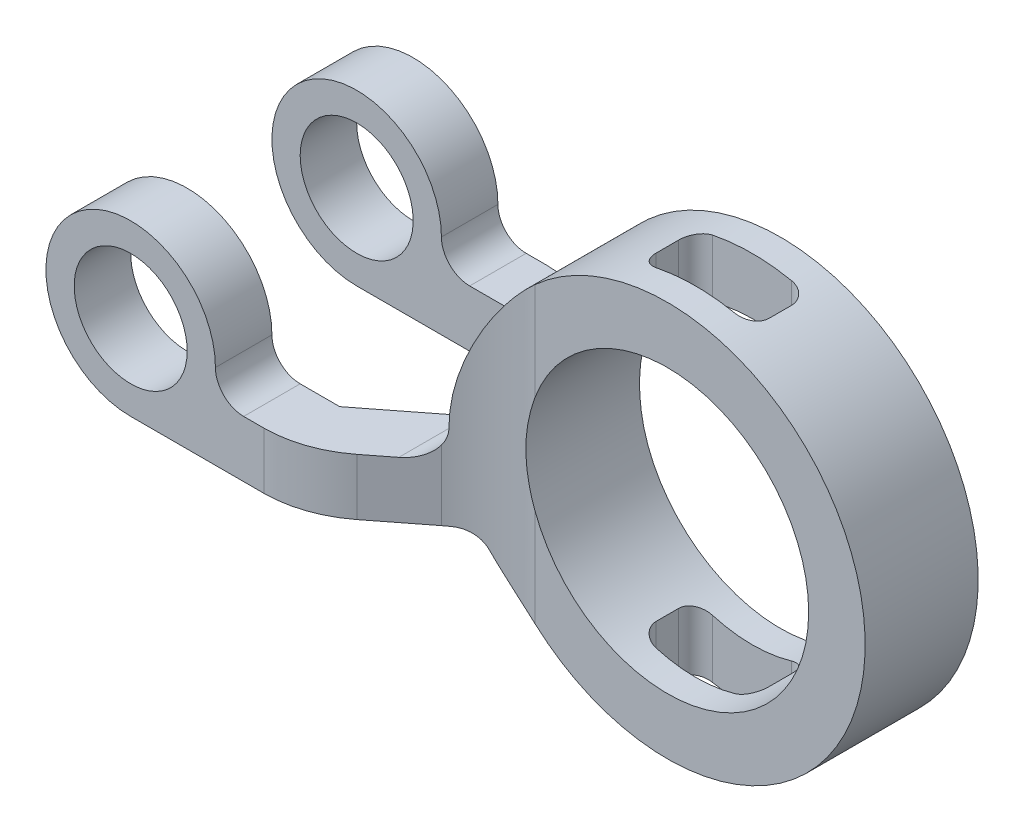
SolidWorks part; units mm, degrees
material "1060 Alloy"
ref_plane "Front Plane" through (0, 0, 0) normal (0, 0, 1) x (1, 0, 0)
ref_plane "Top Plane" through (0, 0, 0) normal (0, 1, 0) x (1, 0, 0)
ref_plane "Right Plane" through (0, 0, 0) normal (1, 0, 0) x (0, 0, -1)
sketch "Sketch1" plane through (0, 0, 0) normal (0, 0, 1) x (1, 0, 0)
  line L0 (-40, -7.5) -> (-17.3205, -7.5)
  line L2 (-30, -2.5) -> (-20, -2.5)
  circle A0 centre (0, 0) radius 12.5
  arc A1 (-15.1554, -8.75) -> (-17.5, 0) centre (0, 0) ccw
  arc A2 (-32.5, 0) -> (-40, -7.5) centre (-40, 0) ccw
  circle A3 centre (-40, 0) radius 5
  arc A4 (-20, -2.5) -> (-17.5, 0) centre (-20, 0) ccw
  arc A5 (-17.3205, -7.5) -> (-15.1554, -8.75) centre (-17.3205, -10) cw
  arc A6 (-32.5, 0) -> (-30, -2.5) centre (-30, 0) ccw
  dimension "D1" = 35
  dimension "D2" = 25
  dimension "D3" = 15
  dimension "D4" = 10
  dimension "D7" = 2.5
  dimension "D5" = 40
  dimension "D6" = 5
extrude "Boss-Extrude3" add sketch "Sketch1" along normal mid plane 25
sketch "Sketch3" plane through (0, -7.5, 0) normal (0, -1, 0) x (1, 0, 0)
  line L0 (-24.7822, 12.5) -> (-15.1554, 5)
  line L1 (-15.1554, -5) -> (-24.7822, -12.5)
  line L2 (-24.7822, -12.5) -> (17.5, -12.5)
  line L3 (-24.7822, 12.5) -> (17.5, 12.5)
  line L5 (-47.5, -7.5) -> (-26.5, -7.5)
  line L6 (-26.5, -7.5) -> (-18.3921, -1.1833)
  line L7 (-18.3921, 1.1833) -> (-26.5, 7.5)
  line L8 (-26.5, 7.5) -> (-47.5, 7.5)
  line L9 (-47.5, -7.5) -> (-47.5, 7.5)
  line L11 (-40, 12.5) -> (-40, -12.5) construction
  line L12 (-15.1554, 12.5) -> (-15.1554, -12.5) construction
  line L13 (-47.5, 12.5) -> (-47.5, -12.5) construction
  line L15 (-20, 12.5) -> (-30, 12.5) construction
  line L18 (-15.1554, 5) -> (17.5, 5)
  line L19 (17.5, -12.5) -> (17.5, 12.5) construction
  line L20 (17.5, 5) -> (17.5, 12.5)
  line L21 (-15.1554, -5) -> (17.5, -5)
  line L22 (17.5, -5) -> (17.5, -12.5)
  arc A0 (-18.3921, -1.1833) -> (-18.3921, 1.1833) centre (-19.3139, 0) ccw
  point P2 (-47.5, 0)
  point P14 (-28.1768, 7.5)
  dimension "D4" = 5
  dimension "D5" = 1.5
  dimension "D6" = 13.5
  dimension "D1" = 15
  dimension "D2" = 10
  dimension "D3" = 5
extrude "Cut-Extrude2" cut sketch "Sketch3" against normal through all both and the other way through all
fillet "Fillet1" radius 10 4 edges at (-24.7822, -5, 12.5) (-24.7822, -5, -12.5) (-15.1554, 0, -5) (-15.1554, 0, 5)
sketch "Sketch4" plane through (0, 0, 0) normal (0, 1, 0) x (1, 0, 0)
  line L1 (-3.5, -2.5) -> (3.5, -2.5)
  line L2 (-5, -1) -> (-5, 1)
  line L3 (-3.5, 2.5) -> (3.5, 2.5)
  line L4 (5, -1) -> (5, 1)
  line L5 (-5, -2.5) -> (5, 2.5) construction
  line L6 (-5, 2.5) -> (5, -2.5) construction
  arc A0 (-3.5, -2.5) -> (-5, -1) centre (-3.5, -1) cw
  arc A1 (3.5, -2.5) -> (5, -1) centre (3.5, -1) ccw
  arc A2 (3.5, 2.5) -> (5, 1) centre (3.5, 1) cw
  arc A3 (-5, 1) -> (-3.5, 2.5) centre (-3.5, 1) cw
  point P0 (0, 0)
  dimension "D3" = 1.5
  dimension "D1" = 10
  dimension "D2" = 5
extrude "Cut-Extrude3" cut sketch "Sketch4" against normal through all both and the other way through all
